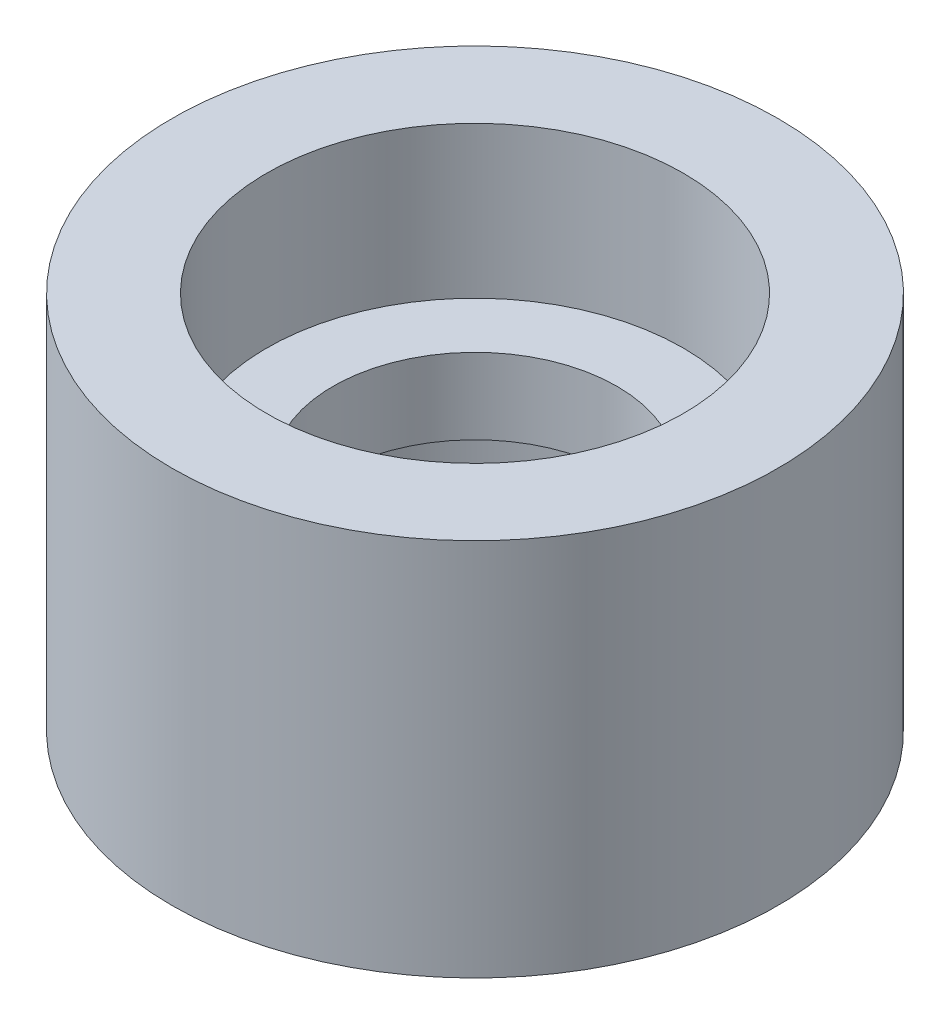
SolidWorks part; units mm, degrees
ref_plane "Front Plane" through (0, 0, 0) normal (0, 0, 1) x (1, 0, 0)
ref_plane "Top Plane" through (0, 0, 0) normal (0, 1, 0) x (1, 0, 0)
ref_plane "Right Plane" through (0, 0, 0) normal (1, 0, 0) x (0, 0, -1)
ref_axis "X" through (88.99, 0, 0) along (-1, 0, 0)
ref_axis "Y" through (0, 55, 0) along (0, -1, 0)
ref_axis "Z" through (0, 0, -88.99) along (0, 0, 1)
sketch "Sketch4" plane through (0, 0, 0) normal (0, 0, 1) x (1, 0, 0)
  line L0 (0, 0) -> (0, 42.3652) construction
  line L1 (-11, 0) -> (-16, 0)
  line L3 (-16, 0) -> (-16, 20)
  line L4 (-16, 20) -> (-11, 20)
  line L5 (-11, 20) -> (-11, 12)
  line L6 (-11, 12) -> (-7.5, 12)
  line L7 (-7.5, 12) -> (-7.5, 8)
  line L8 (-7.5, 8) -> (-11, 8)
  line L9 (-11, 8) -> (-11, 0)
  dimension "D1" = 32
  dimension "D2" = 22
  dimension "D3" = 20
  dimension "D4" = 8
  dimension "D5" = 15
revolve "Revolve1" add sketch "Sketch4" angle 360 about L0
